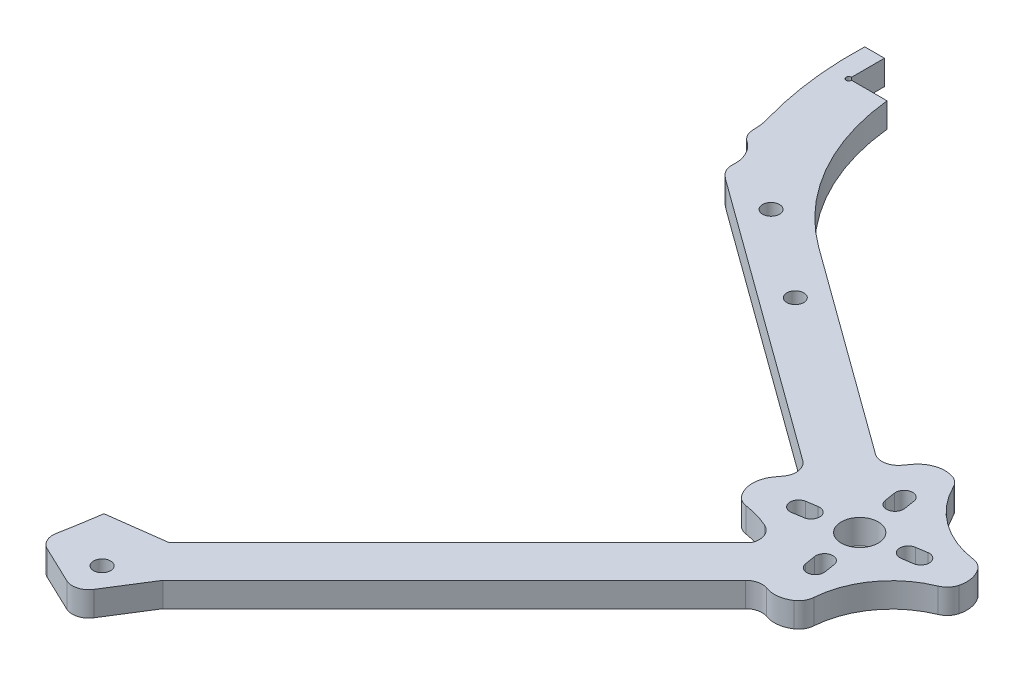
SolidWorks part; units mm, degrees
material "PPS"
ref_plane "前视基准面" through (0, 0, 0) normal (0, 0, 1) x (1, 0, 0)
ref_plane "上视基准面" through (0, 0, 0) normal (0, 1, 0) x (1, 0, 0)
ref_plane "右视基准面" through (0, 0, 0) normal (1, 0, 0) x (0, 0, -1)
sketch "草图3" plane through (0, 0, 0) normal (0, 1, 0) x (1, 0, 0)
  line L0 (0, 0) -> (35.4735, 0) construction
  line L1 (0, 0) -> (62.3757, -45.3186) construction
  line L2 (41.1319, -24.0128) -> (94.6944, -62.9282)
  line L3 (94.6944, -62.9282) -> (100.1314, -55.4448)
  line L4 (100.1314, -55.4448) -> (122.7839, -71.9028)
  line L5 (122.7839, -71.9028) -> (106.3259, -94.5552)
  line L6 (83.6734, -78.0972) -> (106.3259, -94.5552) construction
  line L9 (77.9994, -109.7251) -> (128.6275, -40.0415) construction
  line L11 (103.2286, -75) -> (90.242, -77.0569) construction
  line L13 (110.8832, -73.7876) -> (112.8586, -73.4748) construction
  line L14 (110.6408, -72.2567) -> (112.6161, -71.9438)
  line L15 (111.1257, -75.3185) -> (113.1011, -75.0057)
  line L16 (102.0163, -67.3454) -> (101.7034, -65.37) construction
  line L17 (103.5472, -67.1029) -> (103.2343, -65.1276)
  line L18 (100.4854, -67.5879) -> (100.1725, -65.6125)
  line L19 (95.5741, -76.2124) -> (93.5987, -76.5252) construction
  line L20 (95.8165, -77.7433) -> (93.8412, -78.0562)
  line L21 (95.3316, -74.6815) -> (93.3562, -74.9943)
  line L22 (104.441, -82.6546) -> (104.7539, -84.63) construction
  line L23 (102.9101, -82.8971) -> (103.223, -84.8724)
  line L24 (105.9719, -82.4121) -> (106.2848, -84.3875)
  line L36 (68.8077, -72) -> (90.242, -72) construction
  line L51 (41.6712, -139.6547) -> (94.9997, -86.3262)
  line L52 (94.9997, -86.3262) -> (83.6734, -78.0972)
  line L58 (47.1809, -146.1658) -> (101.962, -91.3847)
  line L61 (101.962, -91.3847) -> (106.3259, -94.5552)
  line L63 (31.6811, -151.7709) -> (40.8875, -156.1591)
  line L64 (47.1809, -146.1658) -> (40.8875, -156.1591)
  line L65 (41.6712, -139.6547) -> (31.2614, -141.0241)
  line L66 (42.309, -153.902) -> (47.6512, -145.4189) construction
  line L67 (31.6811, -151.7709) -> (38.4796, -155.0114) construction
  line L68 (89.1104, -70.6138) -> (83.6734, -78.0972)
  line L69 (35.5479, -31.6984) -> (89.1104, -70.6138)
  circle A5 centre (103.2286, -75) radius 3.375
  arc A6 (110.6408, -72.2567) -> (111.1257, -75.3185) centre (110.8832, -73.7876) ccw
  arc A7 (113.1011, -75.0057) -> (112.6161, -71.9438) centre (112.8586, -73.4748) ccw
  arc A8 (103.5472, -67.1029) -> (100.4854, -67.5879) centre (102.0163, -67.3454) cw
  arc A9 (100.1725, -65.6125) -> (103.2343, -65.1276) centre (101.7034, -65.37) cw
  arc A10 (95.8165, -77.7433) -> (95.3316, -74.6815) centre (95.5741, -76.2124) ccw
  arc A11 (93.3562, -74.9943) -> (93.8412, -78.0562) centre (93.5987, -76.5252) ccw
  arc A12 (102.9101, -82.8971) -> (105.9719, -82.4121) centre (104.441, -82.6546) cw
  arc A13 (106.2848, -84.3875) -> (103.223, -84.8724) centre (104.7539, -84.63) cw
  arc A16 (41.1319, -24.0128) -> (35.5479, -31.6984) centre (38.3399, -27.8556) ccw
  circle A17 centre (103.2286, -75) radius 66.25 construction
  circle A18 centre (44.0442, -32) radius 1.55
  circle A19 centre (60.2246, -43.7557) radius 1.55
  circle A28 centre (39.335, -149.4323) radius 1.55
  arc A29 (30.0249, -148.5011) -> (31.2329, -97.7907) centre (-122.0773, -119.5082) ccw construction
  arc A33 (31.2614, -141.0241) -> (30.0249, -148.5011) centre (-122.0773, -119.5082) cw
  arc A34 (30.0249, -148.5011) -> (31.6811, -151.7709) centre (32.9719, -149.0628) ccw construction
  arc A35 (30.0249, -148.5011) -> (31.6811, -151.7709) centre (32.9719, -149.0628) ccw
  point P11 (114.5549, -83.229)
  point P20 (111.8709, -73.6312)
  point P27 (101.8598, -66.3577)
  point P35 (94.5864, -76.3688)
  point P42 (104.5974, -83.6423)
  point P54 (94.9997, -86.3262)
  dimension "D2" = 45
  dimension "D3" = 6.75
  dimension "D4" = 1.55
  dimension "D7" = 14
  dimension "D11" = 132.5
  dimension "D12" = 3.1
  dimension "D26" = 8.5
  dimension "D27" = 3.1
  dimension "D1" = 36
  dimension "D5" = 2
  dimension "D6" = 7.75
  dimension "D8" = 14
  dimension "D9" = 4.75
  dimension "D10" = 75
  dimension "D13" = 32
  dimension "D14" = 20
  dimension "D22" = 72
  dimension "D25" = 45
extrude "凸台-拉伸1" add sketch "草图3" along normal blind 4.5 contours L5 L4 L3 L2 A16 L69 L52 L51 A19 A18 A11 L21 A10 L20 A7 L15 A6 L14 region at (66.9596, 0, 44.7829)
fillet "圆角-美观1" radius 5 4 edges at (100.1314, 2.25, 55.4448) (122.7839, 2.25, 71.9028) (106.3259, 2.25, 94.5552) (83.6734, 2.25, 78.0972)
sketch "草图4" plane through (0, 4.5, 0) normal (0, 1, 0) x (1, 0, 0)
  line L0 (104.1765, -58.3837) -> (118.7388, -68.9638)
  line L1 (119.8449, -75.9478) -> (109.2648, -90.5101)
  line L3 (103.2286, -75) -> (124.6569, -90.5685) construction
  line L4 (103.2286, -75) -> (89.033, -94.5387) construction
  line L5 (87.7185, -81.0362) -> (102.2808, -91.6163)
  line L6 (96.4624, -84.313) -> (94.9997, -86.3262)
  line L7 (41.1319, -24.0128) -> (94.6944, -62.9282) construction
  arc A2 (102.2808, -91.6163) -> (87.7185, -81.0362) centre (86.1651, -98.4859) ccw
  arc A8 (118.7388, -68.9638) -> (104.1765, -58.3837) centre (120.2922, -51.5141) cw
  arc A9 (119.8449, -75.9478) -> (109.2648, -90.5101) centre (124.6569, -90.5685) ccw
  line M97 (87.7185, -81.0362) -> (94.9997, -86.3262)
extrude "圆弧-美观2" cut sketch "草图4" against normal up to next contours A8 L0 | L1 A9 | L6 A2 M97 region at (110.8688, 4.5, 64.4842) region at (113.6066, 4.5, 82.54) region at (92.8302, 4.5, 83.5118)
fillet "圆角-美观3" radius 3 10 edges at (104.1765, 2.25, 58.3837) (118.7388, 2.25, 68.9638) (119.8449, 2.25, 75.9478) (94.6944, 2.25, 62.9282) (40.8875, 2.25, 156.1591) (109.2648, 2.25, 90.5101) (101.962, 2.25, 91.3847) (89.1104, 2.25, 70.6138) (87.7185, 2.25, 81.0362) (96.4624, 2.25, 84.313)
sketch "草图5" plane through (0, 0, 0) normal (0, 1, 0) x (1, 0, 0)
  line L0 (0, 0) -> (132.1913, 0) construction
  line L1 (0, 0) -> (0, 63.0505) construction
  line L2 (41.1319, -24.0128) -> (54.395, -33.649)
  line L3 (30.5, 2.25) -> (26.9026, 2.25)
  line L4 (30.5, 2.25) -> (30.5, -3.25)
  line L5 (30.5, -3.25) -> (30.5, -4.25)
  line L6 (30.5, -4.25) -> (37.4677, -4.25)
  line L7 (41.1319, -24.0128) -> (92.2673, -61.1648) construction
  line L8 (37.3772, -3.25) -> (30.5, -3.25) construction
  line L9 (30.5, -3.25) -> (30.5, 3.25) construction
  line L10 (30.5, 3.25) -> (26.9448, 3.25) construction
  line L11 (41.1319, -24.0128) -> (35.5479, -31.6984)
  line L13 (34.4971, -25.0636) -> (29.8517, -19.5014) construction
  arc A0 (34.4971, -25.0636) -> (41.1319, -24.0128) centre (38.3399, -27.8556) cw construction
  arc A1 (34.4971, -25.0636) -> (35.5479, -31.6984) centre (38.3399, -27.8556) ccw construction
  arc A2 (29.8211, -20.7007) -> (35.5479, -31.6984) centre (43.7171, -20.4546) ccw
  arc A3 (29.8211, -20.7007) -> (29.4289, -18.099) centre (19.8227, -20.8778) ccw
  arc A6 (26.9026, 2.25) -> (29.4289, -18.099) centre (91.9966, 0) ccw
  arc A7 (29.8202, 19.4008) -> (29.8202, -19.4008) centre (91.9966, 0) ccw construction
  arc A8 (54.395, -33.649) -> (37.3772, -3.25) centre (78.8424, 0) cw construction
  arc A9 (29.4289, -18.099) -> (26.9448, 3.25) centre (91.9966, 0) cw construction
  arc A12 (41.1319, -24.0128) -> (35.5479, -31.6984) centre (38.3399, -27.8556) ccw construction
  arc A14 (54.395, 33.649) -> (54.395, -33.649) centre (78.8424, 0) ccw construction
  arc A15 (37.4677, -4.25) -> (42.5499, -20.3171) centre (78.8424, 0) ccw
  arc A16 (54.395, -33.649) -> (42.5499, -20.3171) centre (78.8424, 0) cw
  dimension "D1" = 3.25
  dimension "D5" = 1
  dimension "D2" = 3.25
  dimension "D3" = 30.5
  dimension "D4" = 1
extrude "机臂配合防旋转" add sketch "草图5" along normal up to surface (4.5 mm away) up to face at (39.335, 4.5, 150.9823)
sketch "草图7" plane through (0, 0, 0) normal (0, 1, 0) x (1, 0, 0)
  circle A1 centre (44.0442, -32) radius 1.55 construction
  circle A6 centre (28, -28) radius 3.15 construction
  circle A7 centre (28, -28) radius 5.5
  dimension "D1" = 11
  dimension "D2" = 1.55
  dimension "D3" = 4
extrude "减震球让位" cut sketch "草图7" along normal through all
fillet "圆角1" radius 3 2 edges at (33.2595, 2.25, 29.6087) (30.034, 2.25, 22.8899)
sketch "草图8" plane through (0, 4.5, 0) normal (0, 1, 0) x (1, 0, 0)
  circle A0 centre (30.5, -4.25) radius 0.5
  dimension "D1" = 1
extrude "直角约束" cut sketch "草图8" against normal through all
